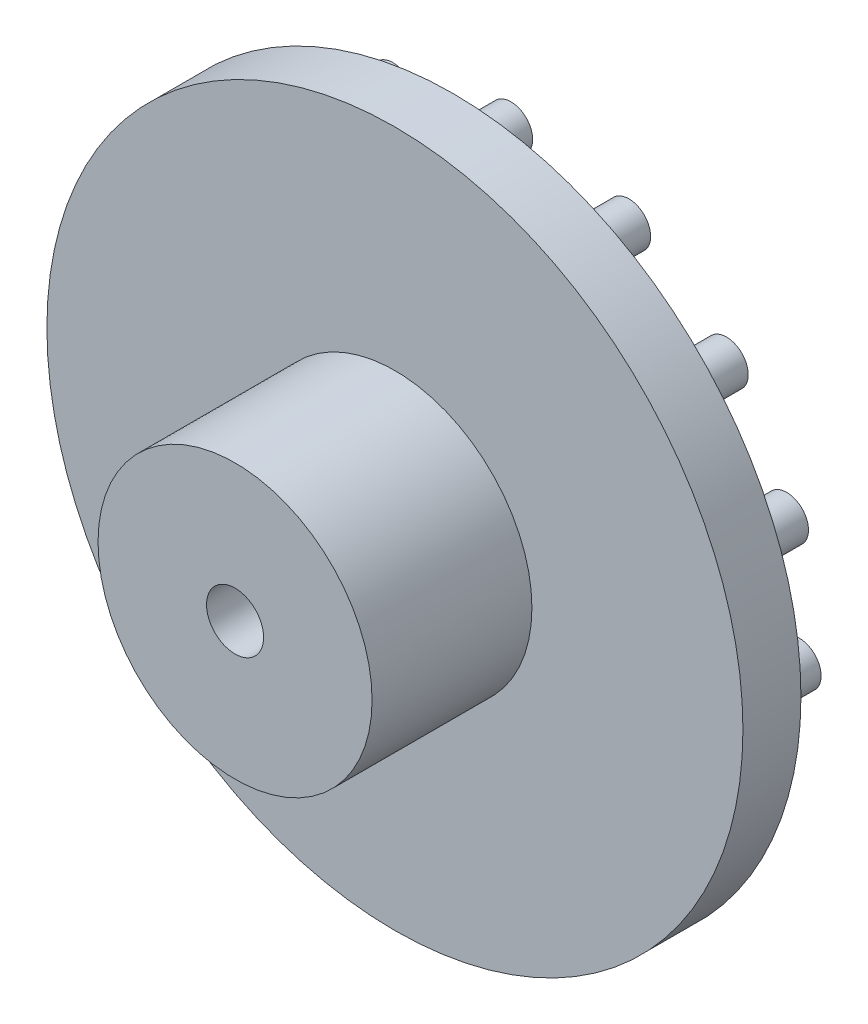
SolidWorks part; units mm, degrees
material "ABS"
ref_plane "Front Plane" through (0, 0, 0) normal (0, 0, 1) x (1, 0, 0)
ref_plane "Top Plane" through (0, 0, 0) normal (0, 1, 0) x (1, 0, 0)
ref_plane "Right Plane" through (0, 0, 0) normal (1, 0, 0) x (0, 0, -1)
sketch "Sketch1" plane through (0, 0, 0) normal (0, 0, 1) x (1, 0, 0)
  circle A0 centre (0, 0) radius 4.55
  circle A1 centre (0, 0) radius 15.24
  dimension "D1" = 9.1
  dimension "D2" = 30.48
extrude "Boss-Extrude1" add sketch "Sketch1" along normal blind 2.54
sketch "Sketch2" plane through (0, 0, 2.54) normal (0, 0, 1) x (1, 0, 0)
  circle A0 centre (0, 0) radius 6
  dimension "D1" = 12
extrude "Boss-Extrude2" add sketch "Sketch2" along normal blind 7
sketch "Sketch3" plane through (0, 0, 9.54) normal (0, 0, 1) x (1, 0, 0)
  line L1 (3.6662, 6.35) -> (-3.6662, 6.35)
  line L2 (-3.6662, 6.35) -> (-7.3323, 0)
  line L3 (-7.3323, 0) -> (-3.6662, -6.35)
  line L4 (-3.6662, -6.35) -> (3.6662, -6.35)
  line L5 (3.6662, -6.35) -> (7.3323, 0)
  line L6 (7.3323, 0) -> (3.6662, 6.35)
  circle A1 centre (0, 0) radius 6.35 construction
  dimension "D1" = 12.7
extrude "Boss-Extrude3" [suppressed] add sketch "Sketch3" along normal blind 38.1
sketch "Sketch4" [suppressed] plane through (0, 0, 47.64) normal (0, 0, 1) x (1, 0, 0)
  line L1 (-0.635, 1.905) -> (0.635, 1.905)
  line L2 (-0.635, 1.905) -> (-0.635, 4.445)
  line L3 (-0.635, 4.445) -> (0.635, 4.445)
  line L4 (0.635, 1.905) -> (0.635, 4.445)
  point P4 (0, 1.905)
  dimension "D1" = 2.54
  dimension "D2" = 1.905
  dimension "D3" = 1.27
extrude "Boss-Extrude4" [suppressed] add sketch "Sketch4" against normal blind 2.54
sketch "Sketch5" plane through (0, 0, 0) normal (0, 0, -1) x (-1, 0, 0)
  line L0 (0, 0) -> (0, 12.7) construction
  circle A0 centre (0, 12.7) radius 0.9525
  circle A13 centre (5.1656, 11.602) radius 0.9525
  circle A14 centre (9.4379, 8.498) radius 0.9525
  circle A15 centre (12.0784, 3.9245) radius 0.9525
  circle A16 centre (12.6304, -1.3275) radius 0.9525
  circle A17 centre (10.9985, -6.35) radius 0.9525
  circle A18 centre (7.4649, -10.2745) radius 0.9525
  circle A19 centre (2.6405, -12.4225) radius 0.9525
  circle A20 centre (-2.6405, -12.4225) radius 0.9525
  circle A21 centre (-7.4649, -10.2745) radius 0.9525
  circle A22 centre (-10.9985, -6.35) radius 0.9525
  circle A23 centre (-12.6304, -1.3275) radius 0.9525
  circle A24 centre (-12.0784, 3.9245) radius 0.9525
  circle A25 centre (-9.4379, 8.498) radius 0.9525
  circle A26 centre (-5.1656, 11.602) radius 0.9525
  dimension "D2" = 1.905
  dimension "D1" = 12.7
  dimension "D3" = 15
  dimension "D4" = 12.7
extrude "Boss-Extrude5" add sketch "Sketch5" along normal blind 2.54
sketch "Sketch6" plane through (0, 0, 9.54) normal (0, 0, 1) x (1, 0, 0)
  circle A1 centre (0, 0) radius 6
  circle A2 centre (0, 0) radius 6
  point P1 (0, 0)
  dimension "D1" = 0
hole_wizard "M3x0.5 Tapped Hole1" positions "Sketch6" profile "Sketch7" tap size "M3x0.5" standard "ANSI Metric"
sketch "Sketch7" plane through (0, 0, 9.54) normal (1, 0, 0) x (0, -1, 0)
  line L0 (0, 0) -> (0, 8.2511)
  line L1 (0, 8.2511) -> (1.25, 7.5)
  line L2 (1.25, 7.5) -> (1.25, 0)
  line L5 (1.25, 0) -> (0, 0)
  line L10 (0, 8.2511) -> (-1.25, 7.5) construction
  line L11 (0, -6.35) -> (0, 107.95) construction
  dimension "Tap Drill Dia." = 2.5
  dimension "Tap Drill Depth" = 7.5
  dimension "Drill Angle" = 118
cosmetic thread "Hole Thread1" parameters "D1"=6, "D2"=3
